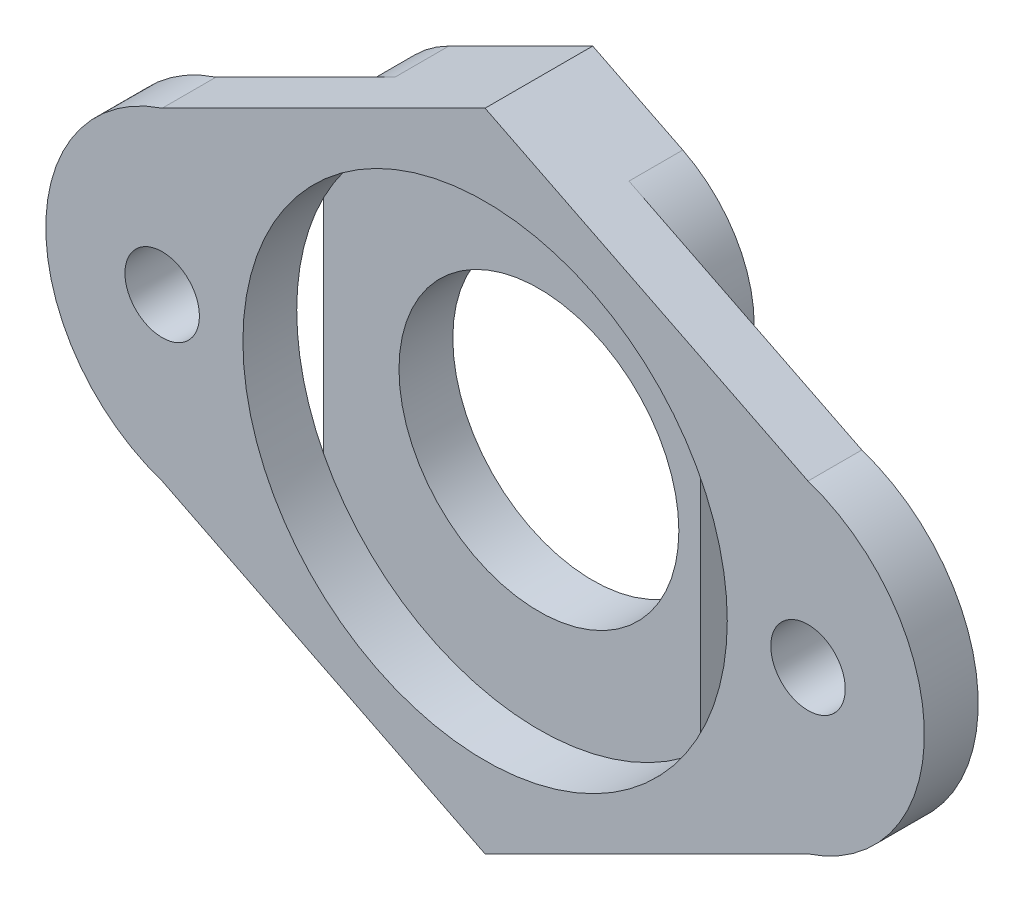
SolidWorks part; units mm, degrees
material "ABS"
ref_plane "Front Plane" through (0, 0, 0) normal (0, 0, 1) x (1, 0, 0)
ref_plane "Top Plane" through (0, 0, 0) normal (0, 1, 0) x (1, 0, 0)
ref_plane "Right Plane" through (0, 0, 0) normal (1, 0, 0) x (0, 0, -1)
sketch "Sketch2" plane through (0, 0, 0) normal (0, 0, 1) x (1, 0, 0)
  line L0 (0, 0) -> (-19.05, -9.525)
  line L2 (0, 0) -> (19.05, -9.525)
  line L3 (-19.05, -28.575) -> (0, -38.1)
  line L4 (0, -38.1) -> (19.05, -28.575)
  arc A0 (-19.05, -28.575) -> (-19.05, -9.525) centre (-15.875, -19.05) cw
  arc A1 (19.05, -9.525) -> (19.05, -28.575) centre (15.875, -19.05) cw
  point P1 (0, -38.1)
  dimension "D1" = 38.1
  dimension "D3" = 19.05
  dimension "D4" = 3.175
  dimension "D5" = 19.05
extrude "Boss-Extrude1" add sketch "Sketch2" along normal blind 6.35
hole_wizard "Tap Drill for #8 Helicoil2" positions "Sketch3" profile "Sketch4" hole size "#8-32" standard "ANSI Inch" end condition through all
sketch "Sketch3" plane through (0, 0, 6.35) normal (0, 0, 1) x (1, 0, 0)
  point P0 (-19.05, -19.05)
  point P3 (19.05, -19.05)
  dimension "D1" = 19.05
  dimension "D2" = 19.05
  dimension "D3" = 19.05
sketch "Sketch4" plane through (-19.05, -19.05, 6.35) normal (1, 0, 0) x (0, -1, 0)
  line L0 (0, 0) -> (0, 6.35)
  line L1 (0, 6.35) -> (2.1971, 6.35)
  line L2 (2.1971, 6.35) -> (2.1971, 0)
  line L5 (2.1971, 0) -> (0, 0)
  line L11 (0, -6.35) -> (0, 107.95) construction
  dimension "Thru Hole Dia." = 4.3942
  dimension "Thru Hole Depth" = 6.35
sketch "Sketch5" plane through (0, 0, 6.35) normal (0, 0, 1) x (1, 0, 0)
  circle A0 centre (0, -19.05) radius 14.2875
  dimension "D1" = 28.575
  dimension "D2" = 19.05
extrude "Cut-Extrude1" cut sketch "Sketch5" against normal blind 3.175
sketch "Sketch6" plane through (0, 0, 0) normal (0, 0, -1) x (-1, 0, 0)
  line L0 (0, 0) -> (19.05, -9.525) construction
  line L1 (12.7, -6.35) -> (25.9152, -6.35)
  line L2 (12.7, -6.35) -> (12.7, -31.75)
  line L3 (12.7, -31.75) -> (25.9152, -31.75)
  line L4 (25.9152, -6.35) -> (25.9152, -31.75)
  line L5 (19.05, -28.575) -> (0, -38.1) construction
  line L6 (-19.05, -9.525) -> (0, 0) construction
  line L7 (-9.525, -4.7625) -> (-25.9152, -4.7625)
  line L8 (-9.525, -4.7625) -> (-9.525, -33.3375)
  line L9 (-9.525, -33.3375) -> (-25.9152, -33.3375)
  line L10 (-25.9152, -4.7625) -> (-25.9152, -33.3375)
  line L11 (0, -38.1) -> (-19.05, -28.575) construction
  arc A0 (19.05, -28.575) -> (19.05, -9.525) centre (15.875, -19.05) ccw construction
  arc A1 (-19.05, -9.525) -> (-19.05, -28.575) centre (-15.875, -19.05) ccw construction
  dimension "D1" = 12.7
extrude "Cut-Extrude2" cut sketch "Sketch6" against normal blind 3.175
fillet "Fillet1" radius 7.62 4 edges at (9.525, -33.3375, 1.5875) (9.525, -4.7625, 1.5875) (-12.7, -6.35, 1.5875) (-12.7, -31.75, 1.5875)
sketch "Sketch7" plane through (0, 0, 0) normal (0, 0, -1) x (-1, 0, 0)
  circle A0 centre (0, -19.05) radius 8.255
  dimension "D1" = 16.51
  dimension "D2" = 19.05
extrude "Cut-Extrude3" cut sketch "Sketch7" against normal through all
